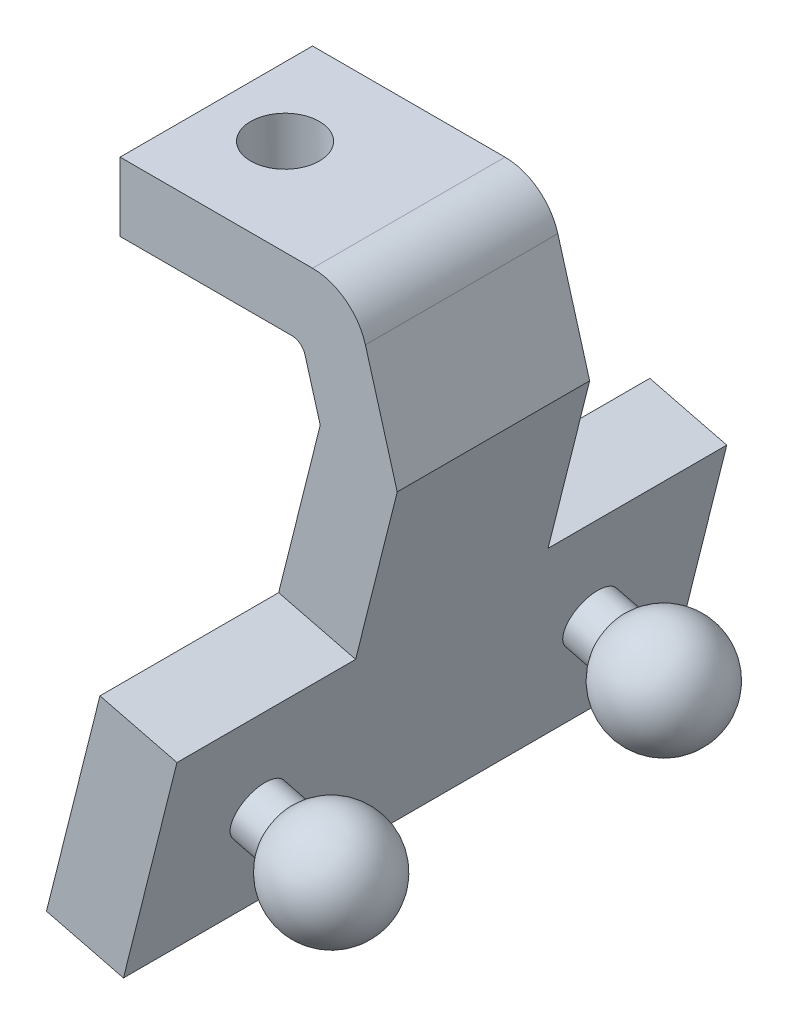
SolidWorks part; units mm, degrees
ref_plane "前视基准面" through (0, 0, 0) normal (0, 0, 1) x (1, 0, 0)
ref_plane "上视基准面" through (0, 0, 0) normal (0, 1, 0) x (1, 0, 0)
ref_plane "右视基准面" through (0, 0, 0) normal (1, 0, 0) x (0, 0, -1)
other "Configuration Table"
sketch "草图1" plane through (0, 0, 0) normal (0, 0, 1) x (1, 0, 0)
  line L0 (0, 0) -> (6.2454, 0)
  line L1 (6.7262, -0.3628) -> (7.2802, -2.304)
  line L2 (7.2802, -2.304) -> (3.8227, -16.0954)
  line L3 (3.8227, -16.0954) -> (6.6228, -16.7974)
  line L4 (6.6228, -16.7974) -> (10.0803, -3.006)
  line L5 (10.0803, -3.006) -> (8.9232, 1.0488)
  line L6 (0, 2.5) -> (7, 2.5)
  line L7 (0, 0) -> (0, 2.5)
  arc A0 (6.2454, 0) -> (6.7262, -0.3628) centre (6.2454, -0.5) cw
  arc A1 (8.9232, 1.0488) -> (7, 2.5) centre (7, 0.5) ccw
  dimension "D1" = 7
  dimension "D3" = 2
  dimension "D6" = 0.5
  dimension "D2" = 2.5
  dimension "D4" = 150
  dimension "D5" = 2.5
extrude "凸台-拉伸1" add sketch "草图1" along normal mid plane 7
sketch "草图2" plane through (0, 0, 0) normal (0, -1, 0) x (1, 0, 0)
  circle A0 centre (2.5, 0) radius 1.25
  dimension "D1" = 2.5
  dimension "D2" = 2.5
extrude "切除-拉伸3" cut sketch "草图2" against normal blind 5.5
sketch "草图3" plane through (10.1932, -2.5554, 0) normal (0.97, -0.2432, 0) x (0, 0, -1)
  line L0 (-3.5, -14.6827) -> (3.5, -14.6827) construction
  line L1 (-10, -6.6827) -> (10, -6.6827)
  line L2 (-10, -6.6827) -> (-10, -14.6827)
  line L3 (-10, -14.6827) -> (10, -14.6827)
  line L4 (10, -6.6827) -> (10, -14.6827)
  line L5 (-10, -6.6827) -> (10, -14.6827) construction
  line L6 (-10, -14.6827) -> (10, -6.6827) construction
  point P0 (0, -10.6827)
  dimension "D1" = 20
  dimension "D2" = 8
extrude "凸台-拉伸2" add sketch "草图3" against normal up to vertex (2.8868 mm away) up to point (3.8227, -16.0954, -3.5)
sketch "草图4" plane through (10.1932, -2.5554, 0) normal (0.97, -0.2432, 0) x (0, 0, -1)
  circle A0 centre (-6.0502, -10.7525) radius 1
  point P2 (-6.0502, -10.7525)
  dimension "D1" = 2
extrude "凸台-拉伸3" add sketch "草图4" along normal blind 1
ref_axis "基准轴1" through (8.4911, -13.214, 6.0502) along (-0.97, 0.2432, 0)
ref_plane "基准面1" through (-2.6147, -10.4298, 0) normal (0.2432, 0.97, 0) x (-0.97, 0.2432, 0)
sketch "草图5" plane through (-2.6147, -10.4298, 0) normal (0.2432, 0.97, 0) x (-0.97, 0.2432, 0)
  line L0 (-11.5087, 6.0502) -> (-15.2407, 6.0502)
  line L1 (-11.5087, 7.0502) -> (-11.5087, 5.0502) construction
  line L2 (-11.5087, 6.0502) -> (-11.5087, 7.0502)
  arc A0 (-11.5087, 7.0502) -> (-15.2407, 6.0502) centre (-13.2407, 6.0502) ccw
  dimension "D1" = 4
revolve "旋转1" add sketch "草图5" angle 360 about L0
mirror "镜向1" about plane through (0, 0, 0) normal (0, 0, 1) of "凸台-拉伸3", "旋转1"
